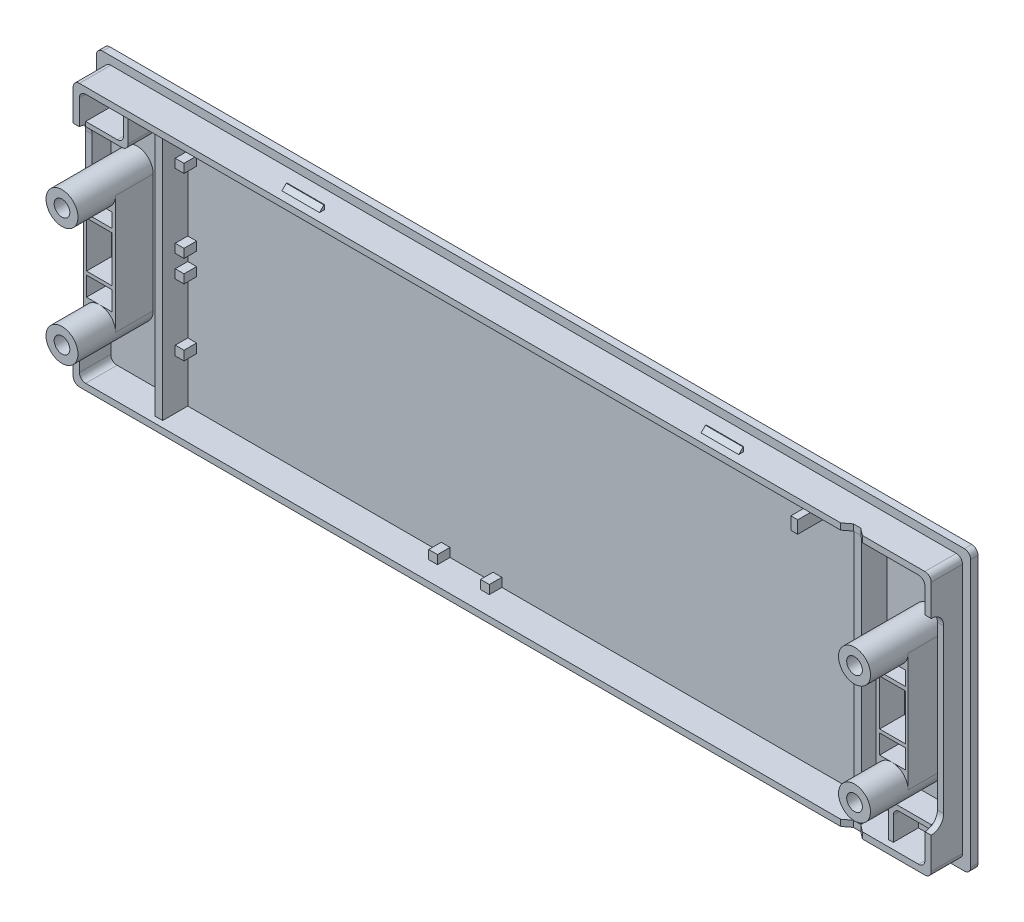
SolidWorks part; units mm, degrees
ref_plane "Front Plane" through (0, 0, 0) normal (0, 0, 1) x (1, 0, 0)
ref_plane "Top Plane" through (0, 0, 0) normal (0, 1, 0) x (1, 0, 0)
ref_plane "Right Plane" through (0, 0, 0) normal (1, 0, 0) x (0, 0, -1)
sketch "Sketch1" plane through (0, 0, 0) normal (0, 0, 1) x (1, 0, 0)
  line L0 (0, 0) -> (0, 44.53) construction
  line L2 (0, 0) -> (139.43, 0)
  line L3 (0, 0) -> (0, 44.53)
  line L4 (0, 44.53) -> (139.43, 44.53)
  line L5 (139.43, 0) -> (139.43, 44.53)
  dimension "D1" = 139.43
  dimension "D2" = 44.53
extrude "Boss-Extrude1" add sketch "Sketch1" along normal blind 1.17
sketch "Sketch2" plane through (0, 0, 1.17) normal (0, 0, 1) x (1, 0, 0)
  line L0 (139.43, 44.53) -> (0, 44.53) construction
  line L1 (1.3, 43.23) -> (138.13, 43.23)
  line L2 (1.3, 43.23) -> (1.3, 1.3)
  line L3 (1.3, 1.3) -> (138.13, 1.3)
  line L4 (138.13, 43.23) -> (138.13, 1.3)
  line L5 (2.3, 42.23) -> (137.13, 42.23)
  line L6 (2.3, 42.23) -> (2.3, 2.3)
  line L7 (2.3, 2.3) -> (137.13, 2.3)
  line L8 (137.13, 42.23) -> (137.13, 2.3)
  line L9 (0, 0) -> (139.43, 0) construction
  line L10 (0, 44.53) -> (0, 0) construction
  line L11 (139.43, 0) -> (139.43, 44.53) construction
  dimension "D1" = 1.3
  dimension "D2" = 1.3
  dimension "D3" = 1.3
  dimension "D4" = 1.3
  dimension "D5" = 1
  dimension "D6" = 1
  dimension "D7" = 1
  dimension "D8" = 1
extrude "Boss-Extrude2" add sketch "Sketch2" along normal blind 5 contours L2 L1 L4 L3 | L6 L5 L8 L7
sketch "Sketch3" plane through (0, 0, 1.17) normal (0, 0, 1) x (1, 0, 0)
  line L0 (2.3, 42.23) -> (137.13, 42.23) construction
  line L1 (13.38, 42.23) -> (14.58, 42.23)
  line L2 (13.38, 42.23) -> (13.38, 2.3)
  line L3 (13.38, 2.3) -> (14.58, 2.3)
  line L4 (14.58, 42.23) -> (14.58, 2.3)
  line L5 (2.3, 2.3) -> (137.13, 2.3) construction
  line L6 (2.3, 42.23) -> (137.13, 42.23) construction
  line L7 (124.85, 42.23) -> (126.05, 42.23)
  line L8 (124.85, 42.23) -> (124.85, 2.3)
  line L9 (124.85, 2.3) -> (126.05, 2.3)
  line L10 (126.05, 42.23) -> (126.05, 2.3)
  line L11 (1.3, 43.23) -> (1.3, 1.3) construction
  line L12 (138.13, 43.23) -> (138.13, 1.3) construction
  dimension "D1" = 1.2
  dimension "D2" = 1.2
  dimension "D3" = 12.08
  dimension "D4" = 12.08
extrude "Boss-Extrude3" add sketch "Sketch3" along normal blind 4
sketch "Sketch4" plane through (0, 0, 1.17) normal (0, 0, 1) x (1, 0, 0)
  line L0 (126.05, 2.3) -> (137.13, 2.3) construction
  line L1 (137.13, 42.23) -> (129.44, 42.23)
  line L2 (137.13, 42.23) -> (137.13, 2.3)
  line L3 (137.13, 2.3) -> (129.44, 2.3)
  line L4 (129.44, 42.23) -> (129.44, 2.3)
  line L5 (2.3, 2.3) -> (137.13, 2.3) construction
  line L6 (2.3, 42.23) -> (9.99, 42.23)
  line L7 (2.3, 42.23) -> (2.3, 2.3)
  line L8 (2.3, 2.3) -> (9.99, 2.3)
  line L9 (9.99, 42.23) -> (9.99, 2.3)
  line L10 (13.38, 42.23) -> (13.38, 2.3) construction
  line L11 (126.05, 2.3) -> (126.05, 42.23) construction
  dimension "D1" = 3.39
  dimension "D2" = 3.39
extrude "Boss-Extrude4" add sketch "Sketch4" along normal blind 11
sketch "Sketch5" plane through (0, 0, 12.17) normal (0, 0, 1) x (1, 0, 0)
  line L0 (129.44, 42.23) -> (129.44, 2.3) construction
  line L1 (137.13, 2.3) -> (129.44, 2.3)
  line L2 (137.13, 2.3) -> (137.13, 9.2)
  line L3 (137.13, 9.2) -> (129.44, 9.2)
  line L4 (129.44, 2.3) -> (129.44, 9.2)
  line L5 (137.13, 2.3) -> (137.13, 42.23) construction
  line L6 (129.44, 42.23) -> (137.13, 42.23)
  line L7 (129.44, 42.23) -> (129.44, 35.33)
  line L8 (129.44, 35.33) -> (137.13, 35.33)
  line L9 (137.13, 42.23) -> (137.13, 35.33)
  line L10 (2.3, 42.23) -> (2.3, 2.3) construction
  line L11 (9.99, 42.23) -> (2.3, 42.23)
  line L12 (9.99, 42.23) -> (9.99, 35.33)
  line L13 (9.99, 35.33) -> (2.3, 35.33)
  line L14 (2.3, 42.23) -> (2.3, 35.33)
  line L15 (9.99, 2.3) -> (9.99, 42.23) construction
  line L16 (2.3, 2.3) -> (9.99, 2.3)
  line L17 (2.3, 2.3) -> (2.3, 9.2)
  line L18 (2.3, 9.2) -> (9.99, 9.2)
  line L19 (9.99, 2.3) -> (9.99, 9.2)
  dimension "D1" = 6.9
extrude "Cut-Extrude1" cut sketch "Sketch5" against normal up to surface (11 mm away) up to face at (127.745, 22.265, 1.17)
sketch "Sketch6" plane through (0, 0, 12.17) normal (0, 0, 1) x (1, 0, 0)
  circle A0 centre (132.9089, 12.7148) radius 2.55
  circle A1 centre (132.9089, 31.6157) radius 2.55
  dimension "D1" = 5.1
  dimension "D2" = 5.1
extrude "Boss-Extrude6" add sketch "Sketch6" along normal blind 2
sketch "Sketch7" plane through (0, 0, 12.17) normal (0, 0, 1) x (1, 0, 0)
  line L0 (129.44, 9.2) -> (129.44, 35.33)
  line L1 (129.44, 35.33) -> (137.13, 35.33)
  line L2 (137.13, 35.33) -> (137.13, 9.2)
  line L3 (137.13, 9.2) -> (129.44, 9.2)
  line L4 (135.4589, 12.7148) -> (135.4589, 31.6157)
  line L5 (130.3589, 12.7148) -> (130.3589, 31.6157)
  arc A0 (130.3589, 12.7148) -> (135.4589, 12.7148) centre (132.9089, 12.7148) ccw
  arc A1 (135.4589, 31.6157) -> (130.3589, 31.6157) centre (132.9089, 31.6157) ccw
  circle M9 centre (132.9089, 31.6157) radius 2.55
  circle M10 centre (132.9089, 12.7148) radius 2.55
extrude "Cut-Extrude3" cut sketch "Sketch7" against normal up to surface (11 mm away) contours L5 L4 M10 M9 | L3 L0 L1 L2 region at (132.9089, 22.1653, 12.17) up to face at (69.715, 22.265, 1.17)
sketch "Sketch8" plane through (0, 0, 14.17) normal (0, 0, 1) x (1, 0, 0)
  circle A0 centre (132.9089, 12.7148) radius 2.55
  circle A1 centre (132.9089, 31.6157) radius 2.55
extrude "Boss-Extrude7" add sketch "Sketch8" against normal up to surface (13 mm away) up to face at (69.715, 22.265, 1.17)
sketch "Sketch9" plane through (0, 0, 12.17) normal (0, 0, 1) x (1, 0, 0)
  line L0 (130.3589, 12.7148) -> (130.3589, 31.6157)
  line L1 (135.4589, 12.7148) -> (135.4589, 31.6157)
  arc A0 (135.4589, 12.7148) -> (130.3589, 12.7148) centre (132.9089, 12.7148) ccw
  arc A1 (130.3589, 31.6157) -> (135.4589, 31.6157) centre (132.9089, 31.6157) ccw
extrude "Cut-Extrude4" cut sketch "Sketch9" against normal blind 5
sketch "Sketch10" plane through (0, 0, 14.17) normal (0, 0, 1) x (1, 0, 0)
  circle A0 centre (132.9089, 12.7148) radius 2.55
  circle A1 centre (132.9089, 31.6157) radius 2.55
extrude "Cut-Extrude5" cut sketch "Sketch10" against normal blind 1
sketch "Sketch11" plane through (0, 0, 7.17) normal (0, 0, 1) x (1, 0, 0)
  line L1 (130.9125, 18.8721) -> (134.9999, 18.8721)
  line L2 (130.9125, 18.8721) -> (130.9125, 26.1852)
  line L3 (130.9125, 26.1852) -> (134.9999, 26.1852)
  line L4 (134.9999, 18.8721) -> (134.9999, 26.1852)
extrude "Cut-Extrude6" cut sketch "Sketch11" against normal blind 4
sketch "Sketch12" plane through (0, 0, 7.17) normal (0, 0, 1) x (1, 0, 0)
  line L0 (130.9125, 18.8721) -> (134.9999, 18.8721) construction
  line L1 (130.9125, 18.3232) -> (134.9999, 18.3232)
  line L2 (130.9125, 18.3232) -> (130.9125, 15.2648)
  line L3 (130.9125, 15.2648) -> (134.9999, 15.2648)
  line L4 (134.9999, 18.3232) -> (134.9999, 15.2648)
  line L5 (130.9125, 26.1852) -> (130.9125, 18.8721) construction
  line L6 (134.9999, 18.8721) -> (134.9999, 26.1852) construction
  line L7 (132.9089, 29.0657) -> (130.9125, 29.0657)
  line L8 (130.9125, 29.0657) -> (130.9125, 26.7984)
  line L9 (130.9125, 26.7984) -> (134.9999, 26.7984)
  line L10 (134.9999, 26.7984) -> (134.9999, 29.0657)
  line L11 (134.9999, 29.0657) -> (132.9089, 29.0657)
  circle A0 centre (132.9089, 12.7148) radius 2.55 construction
  arc A1 (130.3589, 31.6157) -> (135.4589, 31.6157) centre (132.9089, 31.6157) ccw construction
extrude "Cut-Extrude7" cut sketch "Sketch12" against normal up to surface (4 mm away) up to face at (132.9562, 22.5287, 3.17)
sketch "Sketch13" plane through (0, 0, 13.17) normal (0, 0, 1) x (1, 0, 0)
  circle A0 centre (132.9089, 12.7148) radius 1.25
  circle A1 centre (132.9089, 31.6157) radius 1.25
  dimension "D1" = 2.5
  dimension "D2" = 2.5
extrude "Cut-Extrude8" cut sketch "Sketch13" against normal blind 10
sketch "Sketch14" plane through (0, 0, 12.17) normal (0, 0, 1) x (1, 0, 0)
  line L0 (0, 0) -> (139.43, 0) construction
  line L1 (0, 44.53) -> (69.715, 44.53)
  line L2 (0, 44.53) -> (0, 0)
  line L3 (0, 0) -> (69.715, 0)
  line L4 (69.715, 44.53) -> (69.715, 0)
  dimension "D1" = 69.715
extrude "Cut-Extrude9" cut sketch "Sketch14" against normal through all
mirror "Mirror1" about plane through (69.715, 44.53, 0) normal (1, 0, 0) of bodies 120
fillet "Fillet1" radius 1 8 edges at (0, 44.53, 0.585) (0, 0, 0.585) (139.43, 44.53, 0.585) (139.43, 0, 0.585) (1.3, 43.23, 3.67) (1.3, 1.3, 3.67) (138.13, 43.23, 3.67) (138.13, 1.3, 3.67)
fillet "Fillet2" radius 1 4 edges at (137.13, 2.3, 3.67) (137.13, 42.23, 3.67) (2.3, 2.3, 3.67) (2.3, 42.23, 3.67)
sketch "Sketch15" plane through (0, 0, 1.17) normal (0, 0, 1) x (1, 0, 0)
  line L0 (137.13, 7.7741) -> (130.3589, 7.7741)
  line L1 (137.13, 3.3) -> (137.13, 41.23) construction
  line L2 (130.3589, 7.7741) -> (130.3589, 2.3)
  line L3 (126.05, 2.3) -> (136.13, 2.3) construction
  line L4 (130.3589, 2.3) -> (131.09, 2.3)
  line L5 (131.09, 2.3) -> (131.09, 7.0558)
  line L6 (131.09, 7.0558) -> (137.13, 7.0558)
  line L7 (137.13, 41.23) -> (137.13, 3.3) construction
  line L8 (137.13, 7.0558) -> (137.13, 7.7741)
  line L9 (9.0711, 42.23) -> (9.0711, 36.7559)
  line L10 (13.38, 42.23) -> (3.3, 42.23) construction
  line L11 (9.0711, 36.7559) -> (2.3, 36.7559)
  line L12 (2.3, 41.23) -> (2.3, 3.3) construction
  line L13 (2.3, 36.7559) -> (2.3, 37.4742)
  line L14 (2.3, 37.4742) -> (8.34, 37.4742)
  line L15 (8.34, 37.4742) -> (8.34, 42.23)
  line L16 (8.34, 42.23) -> (9.0711, 42.23)
extrude "Boss-Extrude8" add sketch "Sketch15" along normal up to surface (4 mm away) up to face at (125.45, 22.265, 5.17)
fillet "Fillet3" radius 1 4 edges at (8.34, 37.4742, 3.17) (9.0711, 36.7559, 3.17) (131.09, 7.0558, 3.17) (130.3589, 7.7741, 3.17)
sketch "Sketch16" plane through (0, 0, 1.17) normal (0, 0, 1) x (1, 0, 0)
  circle A0 centre (6.9787, 38.7457) radius 0.8681
  circle A1 centre (132.2483, 5.8316) radius 0.8681
  dimension "D1" = 1.7362
extrude "Cut-Extrude10" cut sketch "Sketch16" against normal through all
sketch "Sketch17" plane through (0, 0, 1.17) normal (0, 0, 1) x (1, 0, 0)
  line L0 (124.85, 42.23) -> (124.85, 2.3) construction
  line L1 (124.85, 37.53) -> (123.45, 37.53)
  line L2 (124.85, 37.53) -> (124.85, 36.13)
  line L3 (124.85, 36.13) -> (123.45, 36.13)
  line L4 (123.45, 37.53) -> (123.45, 36.13)
  line L5 (124.85, 42.23) -> (124.85, 2.3) construction
  line L6 (124.85, 25.79) -> (123.45, 25.79)
  line L7 (124.85, 25.79) -> (124.85, 24.39)
  line L8 (124.85, 24.39) -> (123.45, 24.39)
  line L9 (123.45, 25.79) -> (123.45, 24.39)
  line L10 (124.85, 21.63) -> (123.45, 21.63)
  line L11 (124.85, 21.63) -> (124.85, 20.23)
  line L12 (124.85, 20.23) -> (123.45, 20.23)
  line L13 (123.45, 21.63) -> (123.45, 20.23)
  line L14 (14.58, 2.3) -> (124.85, 2.3) construction
  line L15 (124.85, 10.23) -> (123.45, 10.23)
  line L16 (124.85, 10.23) -> (124.85, 8.83)
  line L17 (124.85, 8.83) -> (123.45, 8.83)
  line L18 (123.45, 10.23) -> (123.45, 8.83)
  line L19 (64.6673, 2.3) -> (63.2673, 2.3)
  line L20 (64.6673, 2.3) -> (64.6673, 3.7)
  line L21 (64.6673, 3.7) -> (63.2673, 3.7)
  line L22 (63.2673, 2.3) -> (63.2673, 3.7)
  line L23 (14.58, 42.23) -> (124.85, 42.23) construction
  line L24 (56.4009, 2.3) -> (55.0009, 2.3)
  line L25 (56.4009, 2.3) -> (56.4009, 3.7)
  line L26 (56.4009, 3.7) -> (55.0009, 3.7)
  line L27 (55.0009, 2.3) -> (55.0009, 3.7)
  line L28 (56.4009, 42.23) -> (55.0009, 42.23)
  line L29 (56.4009, 42.23) -> (56.4009, 40.83)
  line L30 (56.4009, 40.83) -> (55.0009, 40.83)
  line L31 (55.0009, 42.23) -> (55.0009, 40.83)
  line L32 (14.58, 42.23) -> (14.58, 2.3) construction
  line L33 (64.6673, 42.23) -> (63.2673, 42.23)
  line L34 (64.6673, 42.23) -> (64.6673, 40.83)
  line L35 (64.6673, 40.83) -> (63.2673, 40.83)
  line L36 (63.2673, 42.23) -> (63.2673, 40.83)
  line L37 (14.58, 37.53) -> (15.98, 37.53)
  line L38 (14.58, 37.53) -> (14.58, 36.13)
  line L39 (14.58, 36.13) -> (15.98, 36.13)
  line L40 (15.98, 37.53) -> (15.98, 36.13)
  line L42 (14.58, 25.79) -> (15.98, 25.79)
  line L43 (14.58, 25.79) -> (14.58, 24.39)
  line L44 (14.58, 24.39) -> (15.98, 24.39)
  line L45 (15.98, 25.79) -> (15.98, 24.39)
  line L50 (14.58, 22.265) -> (15.98, 22.265)
  line L51 (14.58, 22.265) -> (14.58, 20.865)
  line L52 (14.58, 20.865) -> (15.98, 20.865)
  line L53 (15.98, 22.265) -> (15.98, 20.865)
  line L54 (14.58, 42.23) -> (14.58, 2.3) construction
  line L55 (14.58, 11.7172) -> (15.98, 11.7172)
  line L56 (14.58, 11.7172) -> (14.58, 10.23)
  line L57 (14.58, 10.23) -> (15.98, 10.23)
  line L58 (15.98, 11.7172) -> (15.98, 10.23)
extrude "Boss-Extrude10" add sketch "Sketch17" along normal blind 2
sketch "Sketch18" plane through (0, 0, 1.17) normal (0, 0, 1) x (1, 0, 0)
  line L0 (3.3, 42.23) -> (136.13, 42.23) construction
  line L1 (117.75, 42.23) -> (118.85, 42.23)
  line L2 (117.75, 42.23) -> (117.75, 40.23)
  line L3 (117.75, 40.23) -> (118.85, 40.23)
  line L4 (118.85, 42.23) -> (118.85, 40.23)
  line L5 (124.85, 42.23) -> (124.85, 2.3) construction
  dimension "D1" = 7.1
  dimension "D2" = 1.1
  dimension "D3" = 2
extrude "Boss-Extrude11" add sketch "Sketch18" along normal blind 7
sketch "Sketch19" plane through (0, 42.23, 0) normal (0, -1, 0) x (1, 0, 0)
  line L0 (126.0265, 5.2927) -> (124.8426, 5.2927)
  line L1 (124.8426, 5.2927) -> (123.7013, 6.17)
  line L2 (118.85, 6.17) -> (136.13, 6.17) construction
  line L3 (123.7013, 6.17) -> (123.5402, 6.2938)
  line L4 (123.5402, 6.2938) -> (127.3265, 6.2938)
  line L5 (127.3265, 6.2938) -> (126.0265, 5.2927)
  dimension "D1" = 1.0011
  dimension "D2" = 1.3024
  dimension "D3" = 1.3
extrude "Cut-Extrude11" cut sketch "Sketch19" against normal through all both and the other way through all
sketch "Sketch20" plane through (0, 1.3, 0) normal (0, -1, 0) x (1, 0, 0)
  line L0 (2.3, 1.17) -> (137.13, 1.17) construction
  line L1 (33.29, 5.4779) -> (39.29, 5.4779)
  line L2 (33.29, 5.4779) -> (33.29, 4.07)
  line L3 (33.29, 4.07) -> (39.29, 4.07)
  line L4 (39.29, 5.4779) -> (39.29, 4.07)
  line L5 (100.14, 5.4779) -> (106.14, 5.4779)
  line L6 (100.14, 5.4779) -> (100.14, 4.07)
  line L7 (100.14, 4.07) -> (106.14, 4.07)
  line L8 (106.14, 5.4779) -> (106.14, 4.07)
  line L9 (1, 1.17) -> (138.43, 1.17) construction
  line L10 (1.3, 1.17) -> (1.3, 6.17) construction
  line L11 (138.13, 6.17) -> (138.13, 1.17) construction
  dimension "D1" = 6
  dimension "D2" = 1.4079
  dimension "D3" = 2.9
  dimension "D4" = 2.9
  dimension "D5" = 31.99
  dimension "D6" = 31.99
extrude "Boss-Extrude12" add sketch "Sketch20" along normal blind 0.7
chamfer "Chamfer1" distance 1 angle 45 2 edges at (103.14, 0.6, 5.4779) (36.29, 0.6, 5.4779)
sketch "Sketch21" plane through (0, 43.23, 0) normal (0, 1, 0) x (1, 0, 0)
  line L0 (1.3, -6.17) -> (1.3, -1.17) construction
  line L1 (106.14, -5.17) -> (100.14, -5.17)
  line L2 (106.14, -5.17) -> (106.14, -4.07)
  line L3 (106.14, -4.07) -> (100.14, -4.07)
  line L4 (100.14, -5.17) -> (100.14, -4.07)
  line L5 (39.29, -5.17) -> (33.29, -5.17)
  line L6 (39.29, -5.17) -> (39.29, -4.07)
  line L7 (39.29, -4.07) -> (33.29, -4.07)
  line L8 (33.29, -5.17) -> (33.29, -4.07)
  line L9 (138.13, -1.17) -> (138.13, -6.17) construction
  line L10 (2.3, -1.17) -> (137.13, -1.17) construction
  line L11 (138.43, -1.17) -> (1, -1.17) construction
  dimension "D1" = 6
  dimension "D2" = 6
  dimension "D3" = 1.1
  dimension "D4" = 1.1
  dimension "D5" = 31.99
  dimension "D6" = 31.99
  dimension "D7" = 2.9
  dimension "D8" = 2.9
extrude "Boss-Extrude13" add sketch "Sketch21" along normal blind 0.7
chamfer "Chamfer2" distance 1 angle 45 2 edges at (36.29, 43.93, 5.17) (103.14, 43.93, 5.17)
sketch "Sketch22" plane through (1.3, 0, 0) normal (-1, 0, 0) x (0, 0, 1)
  line L0 (4.17, 37.23) -> (4.17, 7.3)
  line L1 (6.17, 42.23) -> (6.17, 2.3) construction
  line L2 (1.17, 2.3) -> (6.17, 2.3) construction
  line L3 (6.17, 42.23) -> (1.17, 42.23) construction
  line L4 (4.17, 37.23) -> (6.17, 37.23)
  line L5 (6.17, 37.23) -> (6.17, 7.3)
  line L6 (6.17, 7.3) -> (4.17, 7.3)
  dimension "D1" = 2
  dimension "D2" = 5
  dimension "D3" = 5
extrude "Cut-Extrude12" cut sketch "Sketch22" against normal up to surface (1 mm away) up to face at (2.3, 29.69, 3.42)
sketch "Sketch23" plane through (138.13, 0, 0) normal (1, 0, 0) x (0, 0, -1)
  line L0 (-6.17, 42.23) -> (-6.17, 2.3) construction
  line L1 (-6.17, 7.3) -> (-4.17, 7.3)
  line L2 (-6.17, 7.3) -> (-6.17, 37.23)
  line L3 (-6.17, 37.23) -> (-4.17, 37.23)
  line L4 (-4.17, 7.3) -> (-4.17, 37.23)
  line L5 (-6.17, 2.3) -> (-1.17, 2.3) construction
  line L6 (-1.17, 42.23) -> (-6.17, 42.23) construction
  dimension "D1" = 5
  dimension "D2" = 5
  dimension "D3" = 2
extrude "Cut-Extrude13" cut sketch "Sketch23" against normal up to surface (1 mm away) up to face at (137.13, 14.84, 3.42)
fillet "Fillet4" radius 2 4 edges at (1.8, 37.23, 4.17) (1.8, 7.3, 4.17) (137.63, 7.3, 4.17) (137.63, 37.23, 4.17)
